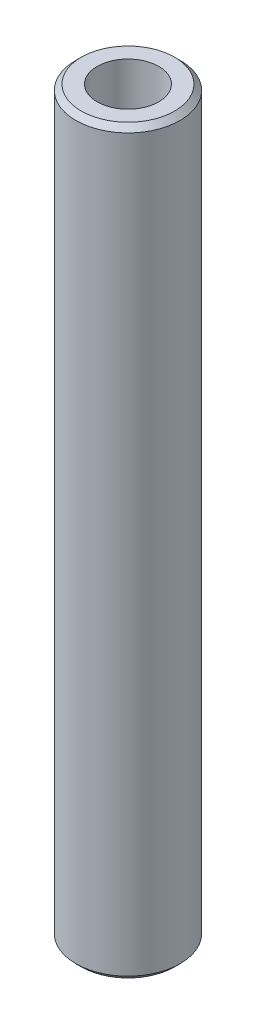
SolidWorks part; units mm, degrees
ref_plane "Front Plane" through (0, 0, 0) normal (0, 0, 1) x (1, 0, 0)
ref_plane "Top Plane" through (0, 0, 0) normal (0, 1, 0) x (1, 0, 0)
ref_plane "Right Plane" through (0, 0, 0) normal (1, 0, 0) x (0, 0, -1)
sketch "Sketch1" plane through (0, 0, 0) normal (0, 1, 0) x (1, 0, 0)
  circle A0 centre (0, 0) radius 17.5
  dimension "SHAFT_OD" = 35
extrude "Boss-Extrude1" add sketch "Sketch1" along normal blind 248.8432
sketch "Sketch2" plane through (0, 0, 0) normal (0, 1, 0) x (1, 0, 0)
  circle A0 centre (0, 0) radius 10.3319
  dimension "BORE_D" = 20.6638
extrude "Cut-Extrude1" cut sketch "Sketch2" along normal through all
chamfer "Chamfer1" distance 1.822 angle 45 2 edges at (0, 248.8432, 17.5) (0, 0, 17.5)
